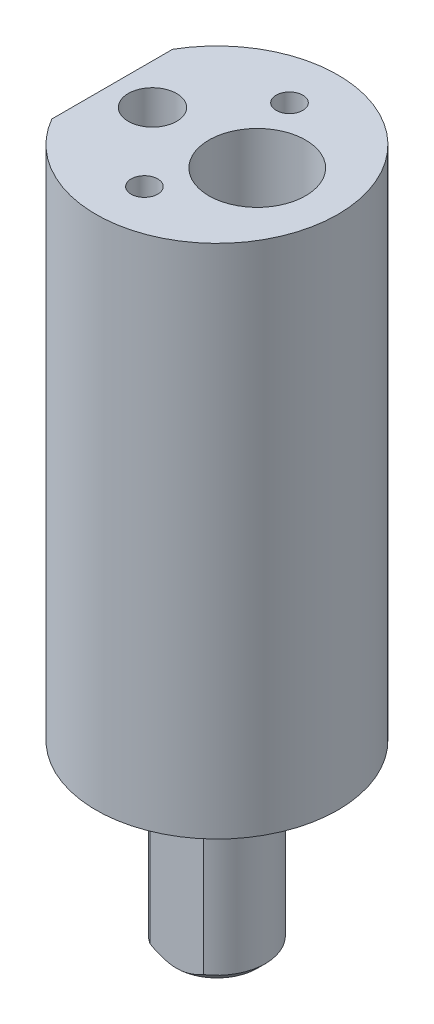
SolidWorks part; units mm, degrees
material "AISI 321 Annealed Stainless Steel (SS)"
ref_plane "Front Plane" through (0, 0, 0) normal (0, 0, 1) x (1, 0, 0)
ref_plane "Top Plane" through (0, 0, 0) normal (0, 1, 0) x (1, 0, 0)
ref_plane "Right Plane" through (0, 0, 0) normal (1, 0, 0) x (0, 0, -1)
sketch "Sketch1" plane through (0, 0, 0) normal (0, 1, 0) x (1, 0, 0)
  line L0 (-3.3166, -5) -> (3.3166, -5)
  arc A0 (3.3166, -5) -> (-3.3166, -5) centre (0, 0) ccw
  dimension "D2" = 12
  dimension "D1" = 5
extrude "Boss-Extrude2" add sketch "Sketch1" along normal blind 22
sketch "Sketch2" plane through (0, 22, 0) normal (0, 1, 0) x (1, 0, 0)
  line L0 (-13, 7.4833) -> (-13, -7.4833)
  arc A0 (-13, -7.4833) -> (-13, 7.4833) centre (0, 0) ccw
  dimension "D1" = 13
  dimension "D2" = 30
extrude "Boss-Extrude3" add sketch "Sketch2" along normal blind 64
sketch "Sketch3" plane through (0, 86, 0) normal (0, 1, 0) x (1, 0, 0)
  line L0 (0, 15) -> (0, -15) construction
  line L1 (-13, 0) -> (0, 0) construction
  line L2 (-13, 7.4833) -> (-13, -7.4833) construction
  arc A0 (-13, -7.4833) -> (-13, 7.4833) centre (0, 0) ccw construction
  circle A1 centre (-8, 0) radius 3
  dimension "D2" = 6
  dimension "D1" = 8
extrude "Cut-Extrude1" cut sketch "Sketch3" against normal blind 65
sketch "Sketch4" plane through (0, 86, 0) normal (0, 1, 0) x (1, 0, 0)
  circle A0 centre (5, 0) radius 6
  dimension "D1" = 12
  dimension "D2" = 5
extrude "Cut-Extrude2" cut sketch "Sketch4" against normal blind 52
hole_wizard "M4 Tapped Hole1" positions "Sketch5" profile "Sketch6" tap size "M4" standard "ISO"
sketch "Sketch5" plane through (0, 86, 0) normal (0, 1, 0) x (1, 0, 0)
  line L0 (0, 15) -> (0, -15) construction
  arc A0 (-13, -7.4833) -> (-13, 7.4833) centre (0, 0) ccw construction
  point P9 (0, 9)
  point P11 (0, -9)
  dimension "D1" = 18
  dimension "D2" = 9
sketch "Sketch6" plane through (0, 86, 9) normal (1, 0, 0) x (0, 0, 1)
  line L0 (0, 0) -> (0, 14.9914)
  line L1 (0, 14.9914) -> (1.65, 14)
  line L2 (1.65, 14) -> (1.65, 0)
  line L5 (1.65, 0) -> (0, 0)
  line L10 (0, 14.9914) -> (-1.65, 14) construction
  line L11 (0, -6.35) -> (0, 107.95) construction
  dimension "Tap Drill Dia." = 3.3
  dimension "Tap Drill Depth" = 14
  dimension "Drill Angle" = 118
cosmetic thread "Hole Thread1" parameters "D1"=13, "D2"=4
cosmetic thread "Hole Thread2" parameters "D1"=13, "D2"=4
sketch "Sketch8" plane through (-13, 0, 0) normal (-1, 0, 0) x (0, 0, 1)
  line L0 (0, 86) -> (0, 22) construction
  line L1 (-7.4833, 86) -> (7.4833, 86) construction
  line L2 (-7.4833, 22) -> (7.4833, 22) construction
  circle A0 centre (0, 54) radius 2.5
  circle A1 centre (0, 25) radius 1.5
  dimension "D1" = 5
  dimension "D2" = 3
  dimension "D3" = 32
  dimension "D4" = 61
extrude "Cut-Extrude3" cut sketch "Sketch8" against normal blind 5
sketch "Sketch9" plane through (-13, 0, 0) normal (-1, 0, 0) x (0, 0, 1)
  line L0 (0, 86) -> (0, 22) construction
  line L1 (-7.4833, 86) -> (7.4833, 86) construction
  line L2 (-3, 22) -> (3, 22) construction
  circle A0 centre (0, 76) radius 1
  circle A1 centre (0, 34) radius 1
  dimension "D1" = 10
  dimension "D3" = 2
  dimension "D2" = 52
extrude "Cut-Extrude4" cut sketch "Sketch9" against normal blind 15
chamfer "Chamfer1" distance 1 angle 45 1 edges at (0, 0, -6)
